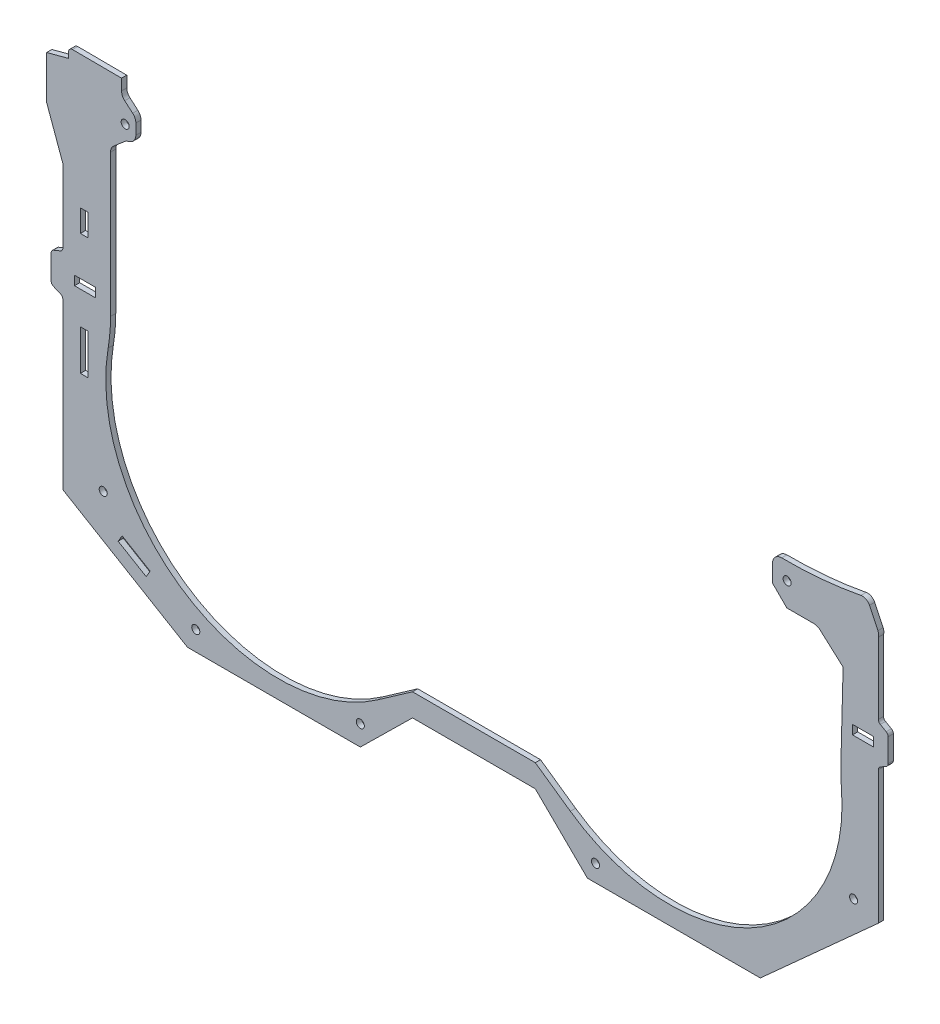
SolidWorks part; units mm, degrees
material "PPS"
ref_plane "前视基准面" through (0, 0, 0) normal (0, 0, 1) x (1, 0, 0)
ref_plane "上视基准面" through (0, 0, 0) normal (0, 1, 0) x (1, 0, 0)
ref_plane "右视基准面" through (0, 0, 0) normal (1, 0, 0) x (0, 0, -1)
sketch "草图1" plane through (0, 0, 0) normal (0, 0, 1) x (1, 0, 0)
  line L0 (-816.4831, 0) -> (39952.7477, 0) construction
  line L1 (0, 10.8762) -> (0, -592.6628) construction
  line L2 (0, 0) -> (206.9686, -284.8678) construction
  line L9 (155.1848, -135.6229) -> (109.8918, -176.4655)
  line L10 (109.8918, -176.4655) -> (43.5772, -176.4655)
  line L60 (-109.8918, -176.4655) -> (-43.5772, -176.4655)
  line L119 (-133.4625, -19.9819) -> (-139.4195, -25.1039)
  line L187 (152.75, -77.5) -> (145.75, -77.5) construction
  line L188 (152.75, -77.5) -> (152.75, -75) construction
  line L189 (145.75, -77.5) -> (145.75, -75) construction
  line L190 (152.75, -75) -> (145.75, -75) construction
  line L191 (-145.75, -75) -> (-152.75, -75) construction
  line L192 (-152.75, -75) -> (-152.75, -77.5) construction
  line L193 (-152.75, -77.5) -> (-145.75, -77.5) construction
  line L194 (-145.75, -77.5) -> (-145.75, -75) construction
  line L195 (145.25, -74.5) -> (153.25, -74.5)
  line L196 (153.25, -74.5) -> (153.25, -78)
  line L197 (153.25, -78) -> (145.25, -78)
  line L198 (145.25, -78) -> (145.25, -74.5)
  line L199 (-153.25, -78) -> (-145.25, -78)
  line L200 (-153.25, -74.5) -> (-153.25, -78)
  line L201 (-145.25, -74.5) -> (-153.25, -74.5)
  line L202 (-145.25, -78) -> (-145.25, -74.5)
  line L204 (-135.1929, 0) -> (-155.5041, 0.108)
  line L205 (-155.5041, 3.8169) -> (-155.5041, -3.6009) construction
  line L206 (-155.5041, 0.108) -> (-155.5041, -3.6009)
  line L207 (-155.5041, -3.6009) -> (-163.9299, -5.8429)
  line L208 (-155.5041, -3.6009) -> (-170.0041, -7.4592) construction
  line L209 (-163.9299, -5.8429) -> (-163.9299, -22.4613)
  line L210 (-163.9299, -22.4613) -> (-157.7253, -39.5836)
  line L211 (-157.7253, -39.5836) -> (-157.7253, -148.0115)
  line L212 (-157.7253, -148.0115) -> (-109.8918, -176.4655)
  line L215 (114.5778, -32.685) -> (114.5778, -42.9165)
  line L216 (120.0778, -48.4165) -> (131.782, -48.4165)
  line L217 (131.782, -48.4165) -> (141.6604, -57.2625)
  line L219 (151.7709, -31.6811) -> (155.0114, -38.4796)
  line L220 (155.1848, -40.6053) -> (155.1848, -135.6229)
  line L221 (120.1823, -39.335) -> (149.4323, -39.335) construction
  line L222 (91.0014, -48.4165) -> (142.5788, -48.4165) construction
  line L223 (75, -103.2286) -> (164.6276, -103.2286) construction
  line L224 (75, -103.2286) -> (37.0006, -157.4975) construction
  line L226 (37.0006, -157.4975) -> (23.5599, -148.0862)
  line L227 (23.5599, -148.0862) -> (-23.5599, -148.0862)
  line L228 (23.5599, -156.7643) -> (-23.5599, -156.7643)
  line L229 (23.5599, -156.7643) -> (43.5772, -176.4655)
  line L230 (-37.0006, -157.4975) -> (-23.5599, -148.0862)
  line L231 (-23.5599, -156.7643) -> (-43.5772, -176.4655)
  line L233 (114.5778, -42.9165) -> (120.0778, -48.4165)
  line L234 (75, -103.2286) -> (140.6832, -94.5813) construction
  line L235 (141.6604, -57.2625) -> (140.6832, -94.5813)
  line L236 (140.6832, -94.5813) -> (140.6832, -61.0285) construction
  line L238 (-139.4195, -87.7629) -> (-75, -103.2286) construction
  line L239 (-75, -103.2286) -> (-141.25, -103.2286) construction
  line L240 (-139.4195, -25.1039) -> (-139.4195, -87.7629)
  line L241 (-135.1929, 0) -> (-135.1929, -5.85)
  line L242 (-135.1929, -5.85) -> (-129.7197, -10.5767)
  line L243 (-129.7197, -10.5767) -> (-129.7197, -18.7984)
  line L244 (-129.7197, -18.7984) -> (-133.4625, -19.9819)
  circle A76 centre (75, -103.2286) radius 66.25 construction
  circle A78 centre (-133.8062, -14.6009) radius 1.55
  arc A79 (155.0114, -38.4796) -> (155.1848, -40.6053) centre (152.3033, -39.7704) cw
  circle A80 centre (-75, -103.2286) radius 66.25 construction
  arc A81 (148.5011, -30.0249) -> (151.7709, -31.6811) centre (149.0628, -32.9719) cw
  arc A82 (153.902, -42.309) -> (155.0114, -38.4796) centre (152.3033, -39.7704) ccw construction
  arc A83 (148.5011, -30.0249) -> (114.5778, -32.685) centre (119.5082, 122.0773) cw
  arc A84 (97.7907, -31.2329) -> (148.5011, -30.0249) centre (119.5082, 122.0773) ccw construction
  circle A85 centre (149.4323, -39.335) radius 1.55 construction
  circle A86 centre (120.1823, -39.335) radius 1.55
  arc A87 (37.0006, -157.4975) -> (141.25, -103.2286) centre (75, -103.2286) ccw
  arc A88 (-37.0006, -157.4975) -> (-141.25, -103.2286) centre (-75, -103.2286) cw
  arc A89 (140.6832, -94.5813) -> (141.25, -103.2286) centre (75, -103.2286) cw
  arc A91 (-141.25, -103.2286) -> (-139.4195, -87.7629) centre (-75, -103.2286) cw
  point P10 (149.25, -75)
  point P29 (0, -148.0862)
  point P38 (153.25, -76.25)
  point P92 (0, -156.7643)
  dimension "D1" = 36
  dimension "D2" = 75
  dimension "D3" = 132.5
  dimension "D6" = 75
  dimension "D7" = 149.25
  dimension "D15" = 125
  dimension "D14" = 3.1
  dimension "D4" = 2.5
  dimension "D5" = 7
  dimension "D8" = 7
  dimension "D9" = 0.5
  dimension "D10" = 0.5
  dimension "D11" = 0.5
  dimension "D12" = 0.5
  dimension "D13" = 29.25
  dimension "D16" = 7.5
  dimension "D17" = 1.5
  dimension "D18" = 13.5
extrude "凸台-拉伸1" add sketch "草图1" along normal blind 2
sketch "草图2" plane through (0, 0, 0) normal (0, 0, 1) x (1, 0, 0)
  line L0 (155.1848, -68.75) -> (158.9348, -70.9151)
  line L1 (155.1848, -135.6229) -> (155.1848, -40.6053) construction
  line L2 (158.9348, -70.9151) -> (158.9348, -81.5849)
  line L3 (158.9348, -81.5849) -> (155.1848, -83.75)
  line L4 (155.1848, -83.75) -> (155.1848, -68.75)
  line L5 (153.25, -76.25) -> (184.2947, -76.25) construction
  line L6 (153.25, -78) -> (153.25, -74.5) construction
  line L7 (-153.25, -76.25) -> (-171.2105, -76.25) construction
  line L8 (-153.25, -74.5) -> (-153.25, -78) construction
  line L9 (-157.7253, -68.75) -> (-157.7253, -83.75)
  line L10 (-157.7253, -39.5836) -> (-157.7253, -148.0115) construction
  line L11 (-157.7253, -83.75) -> (-162.2253, -81.886)
  line L12 (-162.2253, -81.886) -> (-162.2253, -70.614)
  line L13 (-162.2253, -70.614) -> (-157.7253, -68.75)
  dimension "D1" = 3.75
  dimension "D2" = 7.5
  dimension "D3" = 60
  dimension "D4" = 67.5
  dimension "D5" = 4.5
extrude "凸台-拉伸2" add sketch "草图2" against normal up to surface from surface up to face at (-132.2562, -14.6009, 0) starting at face at (149.25, -76.25, 2)
fillet "圆角1" radius 66.25 2 edges at (-139.4195, -87.7629, 1) (140.6832, -94.5813, 1)
fillet "圆角4" radius 1.5 9 edges at (155.1848, -68.75, 1) (158.9348, -70.9151, 1) (155.1848, -83.75, 1) (158.9348, -81.5849, 1) (-155.5041, 0.108, 1) (-157.7253, -68.75, 1) (-162.2253, -70.614, 1) (-162.2253, -81.886, 1) (-157.7253, -83.75, 1)
sketch "板状设备接口" plane through (0, 0, 2) normal (0, 0, 1) x (1, 0, 0)
  line L0 (-151, -90.5) -> (-148, -90.5)
  line L1 (-148, -90.5) -> (-148, -106)
  line L2 (-148, -106) -> (-151, -106)
  line L3 (-151, -106) -> (-151, -90.5)
  line L4 (-148, -77.5) -> (-148, -75) construction
  line L5 (-151, -77.5) -> (-151, -75) construction
  line L6 (-151, -51) -> (-148, -51)
  line L7 (-148, -51) -> (-148, -59.5)
  line L8 (-148, -59.5) -> (-151, -59.5)
  line L9 (-151, -59.5) -> (-151, -51)
  line L10 (-145.25, -74.5) -> (-153.25, -74.5) construction
  line L11 (-153.25, -78) -> (-145.25, -78) construction
  line L12 (-134.9623, -151.9529) -> (-124.2193, -158.3434)
  line L13 (-124.2193, -158.3434) -> (-125.753, -160.9217)
  line L14 (-125.753, -160.9217) -> (-136.496, -154.5312)
  line L15 (-136.496, -154.5312) -> (-134.9623, -151.9529)
  line L21 (-157.7253, -148.0115) -> (-109.8918, -176.4655) construction
  line L22 (-131.1245, -157.7265) -> (-133.8085, -162.2385) construction
  dimension "D1" = 15
  dimension "D2" = 8.5
  dimension "D3" = 12.5
  dimension "D4" = 15.5
  dimension "D5" = 5.25
  dimension "D6" = 12.5
  dimension "D7" = 3
extrude "设备接口" cut sketch "板状设备接口" against normal through all
sketch "草图4" plane through (0, 0, 0) normal (0, 0, 1) x (1, 0, 0)
  line L0 (-157.7253, -84.7523) -> (-157.7253, -148.0115) construction
  line L1 (-109.8918, -176.4655) -> (-43.5772, -176.4655) construction
  line L2 (155.1848, -135.6229) -> (155.1848, -84.616) construction
  line L3 (-43.5772, -168.7155) -> (-43.5772, -176.4655) construction
  line L4 (43.5772, -176.4655) -> (109.8918, -176.4655) construction
  circle A0 centre (-142.2253, -140.8215) radius 1.55
  circle A1 centre (-43.5772, -168.7155) radius 1.55
  circle A2 centre (-106.713, -168.9655) radius 1.55
  circle A3 centre (46.656, -169.9655) radius 1.55
  circle A4 centre (145.6848, -132.301) radius 1.55
  dimension "D5" = 3.1
  dimension "D1" = 15.5
  dimension "D2" = 7.5
  dimension "D3" = 7.75
  dimension "D4" = 9.5
  dimension "D6" = 6.5
extrude "切除-拉伸3" cut sketch "草图4" along normal through all
fillet "圆角5" radius 3.5 7 edges at (131.782, -48.4165, 1) (114.5778, -32.685, 1) (-139.4195, -25.1039, 1) (-129.7197, -10.5767, 1) (-135.1929, -5.85, 1) (-133.4625, -19.9819, 1) (-129.7197, -18.7984, 1)
